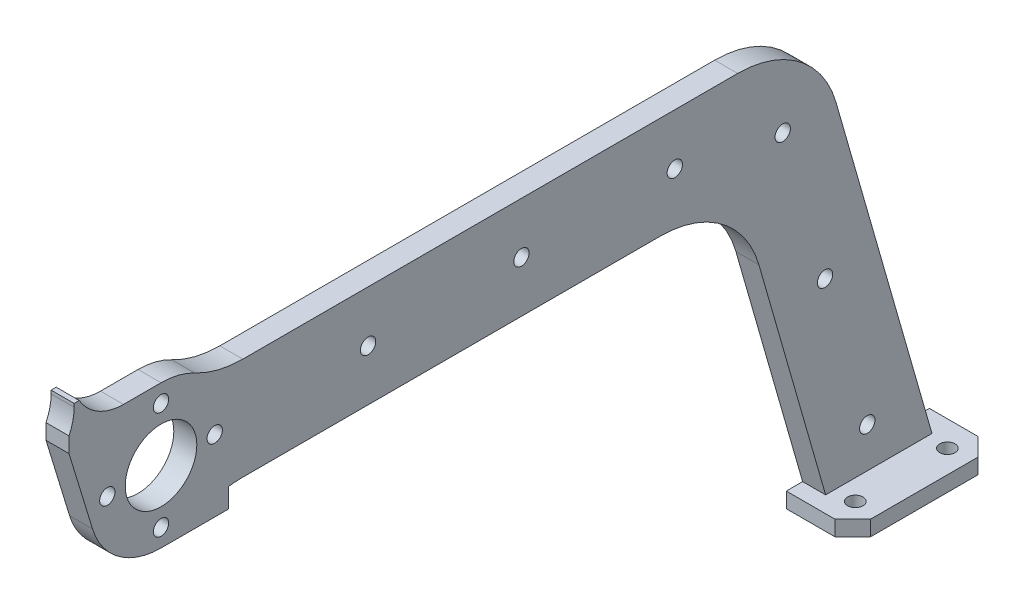
SolidWorks part; units mm, degrees
ref_plane "前视基准面" through (0, 0, 0) normal (0, 0, 1) x (1, 0, 0)
ref_plane "上视基准面" through (0, 0, 0) normal (0, 1, 0) x (1, 0, 0)
ref_plane "右视基准面" through (0, 0, 0) normal (1, 0, 0) x (0, 0, -1)
sketch "草图1" plane through (0, 0, 0) normal (1, 0, 0) x (0, 0, -1)
  line L2 (116.9494, -24.4872) -> (130, -70)
  line L3 (130, -70) -> (150.806, -70)
  line L4 (150.806, -70) -> (132.0205, -4.4873)
  line L5 (112.7953, 10) -> (16, 10)
  line L7 (16, -10) -> (97.7454, -10)
  line L8 (140.8126, -71.4286) -> (116.4936, 13.3819) construction
  line L9 (0, 14) -> (-18, 14)
  line L10 (-18, 14) -> (-18, 11)
  line L11 (-18, 11) -> (-13.3889, -4.091)
  line L12 (13.2242, -14) -> (13.2242, -10)
  line L13 (0, -14) -> (13.2242, -14)
  arc A0 (6.5882, 12.3529) -> (6.5882, -12.3529) centre (0, 0) ccw
  circle A1 centre (0, 0) radius 10.5 construction
  circle A2 centre (0, 0) radius 7
  circle A3 centre (0, 10.5) radius 1.5
  circle A4 centre (10.5, 0) radius 1.5
  circle A5 centre (0, -10.5) radius 1.5
  circle A6 centre (-10.5, 0) radius 1.5
  arc A7 (132.0205, -4.4873) -> (112.7953, 10) centre (112.7953, -10) ccw
  arc A8 (97.7454, -10) -> (116.9494, -24.4872) centre (97.7242, -30) cw
  circle A9 centre (40.5, 0) radius 1.5
  circle A10 centre (70.5, 0) radius 1.5
  circle A11 centre (100.5, 0) radius 1.5
  circle A12 centre (121.61, -4.461) radius 1.5
  circle A13 centre (129.8791, -33.2989) radius 1.5
  circle A14 centre (138.1482, -62.1367) radius 1.5
  arc A15 (16, 10) -> (6.5882, 12.3529) centre (16, 30) cw
  arc A16 (16, -10) -> (6.5882, -12.3529) centre (16, -30) ccw
  point P36 (140.403, -70)
  point P43 (9.798, 7.7889)
  point P50 (9.798, -10)
  dimension "D1" = 28
  dimension "D2" = 21
  dimension "D3" = 14
  dimension "D4" = 3
  dimension "D9" = 20
  dimension "D13" = 3
  dimension "D16" = 30
  dimension "D17" = 3
  dimension "D19" = 30
  dimension "D24" = 20
  dimension "D25" = 20
  dimension "D6" = 106
  dimension "D7" = 20
  dimension "D8" = 130
  dimension "D10" = 70
  dimension "D11" = 20
  dimension "D14" = 40.5
  dimension "D18" = 21.11
  dimension "D20" = 30
  dimension "D21" = 18
  dimension "D22" = 3
  dimension "D26" = 13.2242
  dimension "D28" = 20
  dimension "D15" = 3
  dimension "D5" = 4
extrude "凸台-拉伸1" add sketch "草图1" along normal mid plane 4.5 contours A16 L7 A8 L2 L3 L4 A7 L5 A15 A0 A14 A13 A12 A11 A10 A9 A6 A5 A4 A3 A2 | A0 L9 L10 L11 | L12 A16 A0 region at (0, -12.5569, -110.883) region at (0, -12.6228, -9.4909) region at (0, 9.7023, 13.097)
sketch "草图5" plane through (0, -70, 0) normal (0, -1, 0) x (1, 0, 0)
  line L0 (-2.25, -116.9494) -> (-2.25, -130) construction
  line L1 (-2.25, -126.806) -> (10.75, -126.806)
  line L2 (-2.25, -126.806) -> (-2.25, -154.806)
  line L3 (-2.25, -154.806) -> (10.75, -154.806)
  line L4 (10.75, -126.806) -> (10.75, -154.806)
  line L5 (2.25, -150.806) -> (-2.25, -150.806) construction
  point P8 (-2.25, -161.666)
  point P9 (-2.25, -138.666)
  dimension "D1" = 13
  dimension "D2" = 28
  dimension "D3" = 4
extrude "凸台-拉伸3" add sketch "草图5" along normal blind 3
sketch "草图6" plane through (0, -70, 0) normal (0, 1, 0) x (1, 0, 0)
  line L0 (10.75, 140.806) -> (-2.25, 140.806) construction
  line L1 (10.75, 154.806) -> (10.75, 126.806) construction
  line L2 (-2.25, 150.806) -> (-2.25, 132.0205) construction
  line L5 (2.25, 150.806) -> (2.25, 132.0205) construction
  circle A0 centre (6.25, 149.806) radius 1.5
  circle A1 centre (6.25, 131.806) radius 1.5
  point P12 (2.25, 150.806)
  point P14 (16.2278, 141.666)
  dimension "D3" = 3
  dimension "D1" = 9
  dimension "D2" = 4
extrude "切除-拉伸2" cut sketch "草图6" against normal through all
sketch "草图7" plane through (2.25, 0, 0) normal (1, 0, 0) x (0, 0, -1)
  line L1 (0, 14) -> (-18, 14) construction
  line L2 (-17.0011, 14) -> (-17.0011, 18.9987)
  line L3 (-17.0011, 18.9987) -> (-16.0023, 18.9987)
  line L4 (-16.0023, 18.9987) -> (-16.0023, 14)
  line L5 (-16.0023, 14) -> (-17.0011, 14)
extrude "凸台-拉伸4" add sketch "草图7" against normal up to vertex (4.5 mm away) up to point (-2.25, 14, 0)
fillet "圆角1" radius 10 2 edges at (0, 14, 16.0023) (0, 14, 17.0011)
chamfer "倒角1" distance 3.5 angle 45 2 edges at (10.75, -71.5, -126.806) (10.75, -71.5, -154.806)
